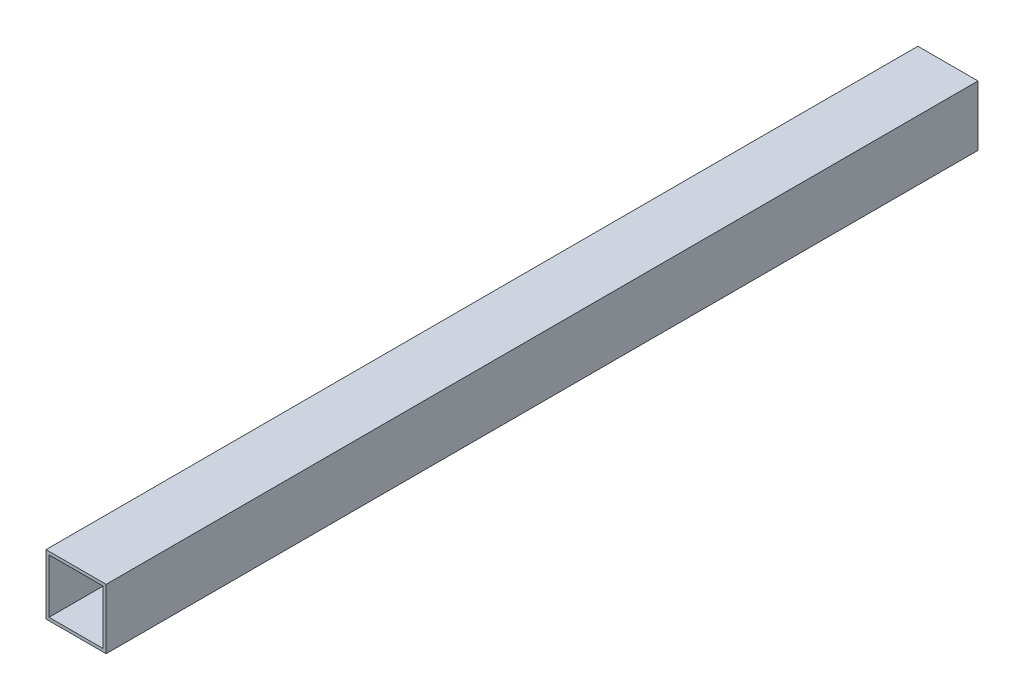
SolidWorks part; units mm, degrees
material "1060 合金"
ref_plane "前视基准面" through (0, 0, 0) normal (0, 0, 1) x (1, 0, 0)
ref_plane "上视基准面" through (0, 0, 0) normal (0, 1, 0) x (1, 0, 0)
ref_plane "右视基准面" through (0, 0, 0) normal (1, 0, 0) x (0, 0, -1)
other "Configuration Table"
sketch "草图1" plane through (0, 0, 0) normal (0, 0, 1) x (1, 0, 0)
  line L1 (0, 0) -> (20, 0)
  line L2 (0, 0) -> (0, -20)
  line L3 (0, -20) -> (20, -20)
  line L4 (20, 0) -> (20, -20)
  dimension "D1" = 20
  dimension "D2" = 20
extrude "拉伸-薄壁1" add sketch "草图1" along normal blind 290 thin thin type one direction reverse wall 1
